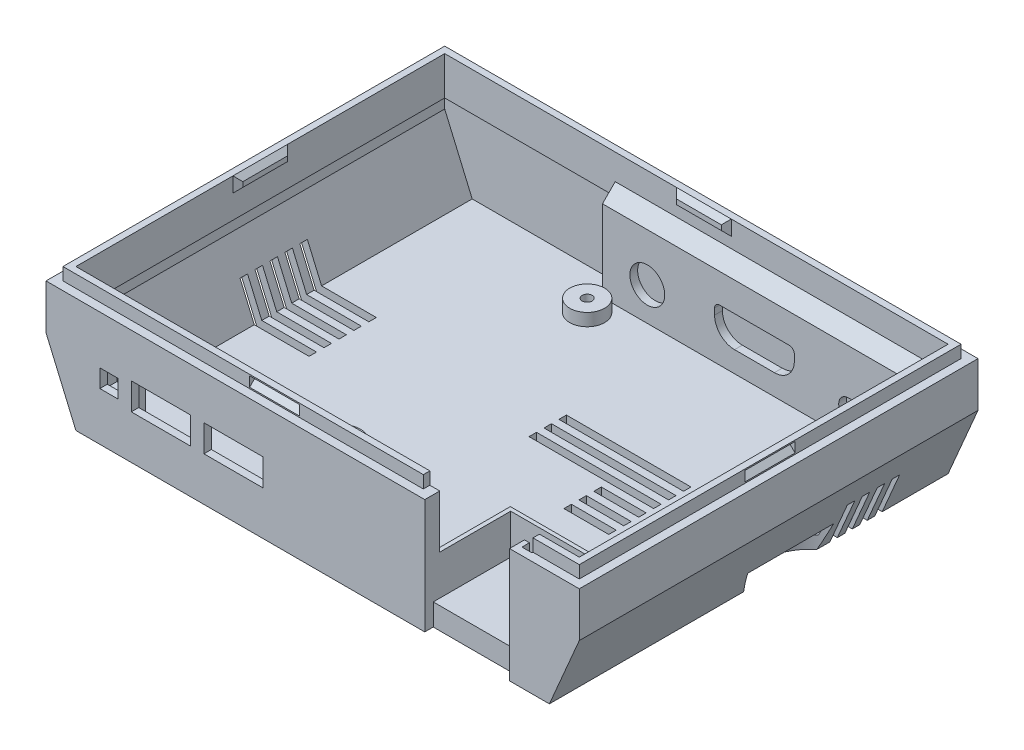
SolidWorks part; units mm, degrees
note: The reader was unsure of these and kept them because the rebuilt part matched: shared geometry of "Sketch7<6>".
ref_plane "Front Plane" through (0, 0, 0) normal (0, 0, 1) x (1, 0, 0)
ref_plane "Top Plane" through (0, 0, 0) normal (0, 1, 0) x (1, 0, 0)
ref_plane "Right Plane" through (0, 0, 0) normal (1, 0, 0) x (0, 0, -1)
sketch "Sketch1" plane through (0, 0, 0) normal (0, 0, 1) x (1, 0, 0)
  line L0 (-41.3082, 11.458) -> (53.6918, 11.458)
  line L1 (-47.3082, 34.458) -> (-47.3082, 25.458)
  line L2 (-47.3082, 25.458) -> (-41.3082, 11.458)
  line L3 (59.6918, 34.458) -> (-47.3082, 34.458)
  line L5 (59.6918, 25.458) -> (53.6918, 11.458)
  line L7 (59.6918, 34.458) -> (59.6918, 25.458)
  dimension "D1" = 95
  dimension "D2" = 107
  dimension "D3" = 9
  dimension "D4" = 107
  dimension "D5" = 23
  dimension "D6" = 6
  dimension "D7" = 9
  dimension "D8" = 11.458
  dimension "D9" = 47.3082
extrude "Boss-Extrude1" add sketch "Sketch1" along normal blind 3
sketch "Sketch2" plane through (0, 0, 3) normal (0, 0, 1) x (1, 0, 0)
  line L0 (-47.3082, 25.458) -> (-41.3082, 11.458) construction
  line L1 (59.6918, 34.458) -> (-47.3082, 34.458) construction
  line L2 (-47.3082, 34.458) -> (-47.3082, 25.458) construction
  line L3 (-47.3082, 34.458) -> (-44.3082, 34.458)
  line L4 (53.6918, 11.458) -> (59.6918, 25.458) construction
  line L5 (59.6918, 34.458) -> (56.6918, 34.458)
  line L6 (-41.3082, 11.458) -> (53.6918, 11.458)
  line L7 (56.6918, 26.0112) -> (56.6918, 34.458)
  line L8 (-44.3082, 26.1347) -> (-38.6611, 12.958)
  line L9 (-44.3082, 34.458) -> (-44.3082, 26.1347)
  line L10 (56.6918, 26.0112) -> (51.7076, 12.958)
  line L14 (59.6918, 25.458) -> (59.6918, 34.458) construction
  line L26 (-47.3082, 34.458) -> (-47.3082, 25.458)
  line L27 (-47.3082, 25.458) -> (-41.3082, 11.458)
  line L28 (53.6918, 11.458) -> (59.6918, 25.458)
  line L29 (59.6918, 25.458) -> (59.6918, 34.458)
  line L34 (-38.6611, 12.958) -> (51.7076, 12.958)
  line L35 (-41.3082, 11.458) -> (53.6918, 11.458) construction
  dimension "D2" = 1.5
extrude "Boss-Extrude2" add sketch "Sketch2" along normal blind 77
sketch "Sketch3" plane through (0, 0, 80) normal (0, 0, 1) x (1, 0, 0)
  line L0 (-47.3082, 34.458) -> (59.6918, 34.458)
  line L12 (-44.3082, 26.1347) -> (-44.3082, 34.458)
  line L13 (-44.3082, 34.458) -> (-47.3082, 34.458)
  line L14 (-47.3082, 34.458) -> (-47.3082, 25.458)
  line L15 (-47.3082, 25.458) -> (-41.3082, 11.458)
  line L16 (-41.3082, 11.458) -> (53.6918, 11.458)
  line L17 (53.6918, 11.458) -> (59.6918, 25.458)
  line L18 (59.6918, 25.458) -> (59.6918, 34.458)
  line L19 (59.6918, 34.458) -> (56.6918, 34.458)
  line L21 (56.6918, 34.458) -> (56.6918, 26.0112)
  line L22 (51.7076, 12.958) -> (-38.6611, 12.958)
  line L25 (56.6918, 26.0112) -> (51.7076, 12.958)
  line L26 (-47.3082, 34.458) -> (-47.3082, 25.458)
  line L27 (-47.3082, 25.458) -> (-41.3082, 11.458)
  line L28 (-41.3082, 11.458) -> (53.6918, 11.458)
  line L29 (53.6918, 11.458) -> (59.6918, 25.458)
  line L30 (59.6918, 25.458) -> (59.6918, 34.458)
  line L32 (-38.6611, 12.958) -> (-44.3082, 26.1347)
  dimension "D1" = 0
extrude "Boss-Extrude3" add sketch "Sketch3" against normal blind 3
sketch "Sketch4" plane through (0, 34.458, 0) normal (0, 1, 0) x (1, 0, 0)
  line L5 (56.6918, -3) -> (-44.3082, -3) construction
  line L7 (56.6918, -77) -> (-44.3082, -77) construction
  line L8 (-45.6082, -78.3) -> (57.9918, -78.3)
  line L9 (57.9918, -78.3) -> (57.9918, -1.7)
  line L10 (57.9918, -1.7) -> (-45.6082, -1.7)
  line L11 (-45.6082, -1.7) -> (-45.6082, -78.3)
  line L12 (-45.6082, -78.3) -> (57.9918, -78.3)
  line L13 (57.9918, -78.3) -> (57.9918, -1.7)
  line L14 (57.9918, -1.7) -> (-45.6082, -1.7)
  line L15 (-45.6082, -1.7) -> (-45.6082, -78.3)
  line L16 (-44.3082, -3) -> (-44.3082, -77)
  line L17 (56.6918, -3) -> (-44.3082, -3)
  line L18 (56.6918, -3) -> (56.6918, -77)
  line L19 (56.6918, -77) -> (-44.3082, -77)
  dimension "D1" = 1.7
extrude "Boss-Extrude4" add sketch "Sketch4" along normal blind 2.5
sketch "Sketch5" plane through (0, 0, 80) normal (0, 0, 1) x (1, 0, 0)
  line L0 (59.6918, 34.458) -> (-47.3082, 34.458) construction
  line L1 (-30.1982, 25.658) -> (-18.3182, 25.658)
  line L2 (-30.1982, 25.658) -> (-30.1982, 20.258)
  line L3 (-30.1982, 20.258) -> (-18.3182, 20.258)
  line L4 (-18.3182, 25.658) -> (-18.3182, 20.258)
  line L5 (-15.6182, 25.658) -> (-3.7382, 25.658)
  line L6 (-15.6182, 25.658) -> (-15.6182, 20.258)
  line L7 (-15.6182, 20.258) -> (-3.7382, 20.258)
  line L8 (-3.7382, 25.658) -> (-3.7382, 20.258)
  line L9 (-36.4982, 24.758) -> (-32.8982, 24.758)
  line L10 (-36.4982, 24.758) -> (-36.4982, 21.158)
  line L11 (-36.4982, 21.158) -> (-32.8982, 21.158)
  line L12 (-32.8982, 24.758) -> (-32.8982, 21.158)
  line L13 (-47.3082, 34.458) -> (-47.3082, 25.458) construction
  line L14 (-45.6082, 34.458) -> (57.9918, 34.458) construction
  dimension "D1" = 5.4
  dimension "D2" = 8.8
  dimension "D3" = 2.7
  dimension "D4" = 5.4
  dimension "D5" = 17.11
  dimension "D6" = 8.8
  dimension "D7" = 9.7
  dimension "D8" = 3.6
  dimension "D9" = 3.6
  dimension "D10" = 10.81
  dimension "D11" = 11.88
  dimension "D12" = 11.88
extrude "Cut-Extrude1" cut sketch "Sketch5" against normal blind 3
sketch "Sketch7" plane through (0, 36.958, 0) normal (0, 1, 0) x (1, 0, 0)
  line L0 (-44.3082, -77) -> (56.6918, -77) construction
  line L1 (29.6918, -77) -> (44.6918, -77)
  line L2 (29.6918, -77) -> (29.6918, -78.3)
  line L3 (29.6918, -78.3) -> (44.6918, -78.3)
  line L4 (44.6918, -77) -> (44.6918, -78.3)
  line L5 (-45.6082, -78.3) -> (57.9918, -78.3) construction
  line L6 (59.6918, -80) -> (59.6918, 0) construction
  line L7 (28.6918, -78.3) -> (45.6918, -78.3)
  line L8 (28.6918, -78.3) -> (28.6918, -81.1052)
  line L9 (28.6918, -81.1052) -> (45.6918, -81.1052)
  line L10 (45.6918, -78.3) -> (45.6918, -81.1052)
  dimension "D1" = 15
  dimension "D2" = 17
  dimension "D3" = 14
  dimension "D4" = 15
extrude "Cut-Extrude4" cut sketch "Sketch7" against normal through all contours L9 L10 L7 L8
extrude "Cut-Extrude5" cut sketch "Sketch7<6>" against normal blind 21.13 contours L1 L4 L3 L2
sketch "Sketch7<6>" plane through (0, 36.958, 0) normal (0, 1, 0) x (1, 0, 0) same geometry as "Sketch7"
sketch "Sketch8" plane through (0, 36.958, 0) normal (0, 1, 0) x (1, 0, 0)
  line L0 (46.1718, -77) -> (48.1718, -77)
  line L1 (44.6918, -77) -> (46.1718, -77)
  line L2 (44.6918, -77) -> (44.6918, -74.2)
  line L3 (44.6918, -74.2) -> (46.1718, -74.2)
  line L5 (44.6918, -77) -> (56.6918, -77) construction
  line L6 (48.1718, -77) -> (46.1718, -74.2)
  dimension "D1" = 1.48
  dimension "D2" = 2.8
  dimension "D3" = 2
extrude "Boss-Extrude5" add sketch "Sketch8" against normal blind 24
sketch "Sketch10" plane through (0, 0, 78.3) normal (0, 0, 1) x (1, 0, 0)
  line L0 (-45.6082, 36.958) -> (29.6918, 36.958) construction
  line L1 (26.7018, 36.958) -> (48.7018, 36.958)
  line L2 (26.7018, 36.958) -> (26.7018, 34.458)
  line L3 (26.7018, 34.458) -> (48.7018, 34.458)
  line L4 (48.7018, 36.958) -> (48.7018, 34.458)
  line L5 (45.6918, 34.458) -> (57.9918, 34.458) construction
  line L6 (57.9918, 36.958) -> (57.9918, 34.458) construction
  point P8 (57.9918, 35.708)
  dimension "D1" = 9.29
  dimension "D2" = 22
extrude "Cut-Extrude6" cut sketch "Sketch10" against normal blind 5
sketch "Sketch11" plane through (0, 12.958, 0) normal (0, 1, 0) x (1, 0, 0)
  line L1 (44.6918, -77) -> (28.9318, -77)
  line L2 (44.6918, -77) -> (44.6918, -62)
  line L3 (44.6918, -62) -> (28.9318, -62)
  line L4 (28.9318, -77) -> (28.9318, -62)
  dimension "D1" = 15
  dimension "D2" = 15.76
extrude "Boss-Extrude6" add sketch "Sketch11" along normal blind 2.87
sketch "Sketch12" plane through (0, 15.828, 0) normal (0, 1, 0) x (1, 0, 0)
  line L5 (29.6918, -76.24) -> (29.6918, -77)
  line L6 (28.9318, -77) -> (29.6918, -77) construction
  line L7 (29.6918, -76.24) -> (30.4518, -76.24)
  line L9 (43.9318, -62.76) -> (44.6918, -62.76)
  line L10 (43.9318, -77.54) -> (43.9318, -74.2)
  line L11 (43.9318, -74.2) -> (43.9318, -62.76)
  line L12 (43.9318, -62.76) -> (29.6918, -62.76)
  line L13 (29.6918, -62.76) -> (29.6918, -76.24)
  line L15 (30.4518, -76.24) -> (30.4518, -77.54)
  line L16 (30.4518, -77.54) -> (43.9318, -77.54)
  line L17 (43.9318, -62.76) -> (29.6918, -62.76)
  line L18 (29.6918, -62.76) -> (29.6918, -76.24)
  line L21 (28.9318, -77) -> (44.6918, -77)
  line L22 (28.9318, -62) -> (28.9318, -77)
  line L23 (44.6918, -62) -> (28.9318, -62)
  line L24 (44.6918, -77) -> (44.6918, -62)
  line L25 (28.9318, -77) -> (29.6918, -77)
  line L26 (28.9318, -62) -> (28.9318, -77)
  line L27 (44.6918, -62) -> (28.9318, -62)
  line L28 (44.6918, -62.76) -> (44.6918, -62)
  dimension "D1" = 0.76
  dimension "D2" = 0
extrude "Boss-Extrude7" add sketch "Sketch12" along normal blind 8
sketch "Sketch15" plane through (-44.3082, 0, 0) normal (1, 0, 0) x (0, 0, -1)
  line L0 (-3, 36.958) -> (-77, 36.958) construction
  line L1 (-45.5, 36.958) -> (-34.5, 36.958)
  line L2 (-45.5, 36.958) -> (-45.5, 33.958)
  line L3 (-45.5, 33.958) -> (-34.5, 33.958)
  line L4 (-34.5, 36.958) -> (-34.5, 33.958)
  line L5 (-77, 26.1347) -> (-77, 36.958) construction
  dimension "D1" = 3
  dimension "D2" = 11
  dimension "D3" = 31.5
extrude "Boss-Extrude8" add sketch "Sketch15" along normal blind 1
chamfer "Chamfer2" distance 1 angle 45 4 edges at (-43.3082, 35.458, 34.5) (-43.3082, 33.958, 40) (-43.3082, 35.458, 45.5) (-43.3082, 36.958, 40)
sketch "Sketch16" plane through (-45.6082, 0, 0) normal (-1, 0, 0) x (0, 0, 1)
  line L0 (1.7, 36.958) -> (78.3, 36.958) construction
  line L1 (35, 36.708) -> (45, 36.708)
  line L2 (35, 36.708) -> (35, 34.708)
  line L3 (35, 34.708) -> (45, 34.708)
  line L4 (45, 36.708) -> (45, 34.708)
  line L5 (1.7, 36.958) -> (1.7, 34.458) construction
  point P6 (1.7, 35.708)
  dimension "D1" = 10
  dimension "D2" = 0.25
  dimension "D3" = 2
  dimension "D4" = 33.3
extrude "Cut-Extrude8" cut sketch "Sketch16" against normal blind 1.5
chamfer "Chamfer3" distance 1.5 angle 45 2 edges at (-44.1082, 36.708, 40) (-44.1082, 34.708, 40)
ref_plane "Plane1" through (6.1918, 0, 0) normal (-1, 0, 0) x (0, 0, 1)
mirror "Mirror1" about plane through (6.1918, 0, 0) normal (-1, 0, 0) of "Chamfer3", "Cut-Extrude8", "Chamfer2", "Boss-Extrude8"
ref_plane "Plane2" through (0, 0, 40) normal (0, 0, 1) x (1, 0, 0)
sketch "Sketch34" plane through (40.6642, -5.0481, 3) normal (0, 0, 1) x (1, 0, 0)
  line L1 (-38.4724, 42.006) -> (-27.4724, 42.006)
  line L2 (-38.4724, 42.006) -> (-38.4724, 39.006)
  line L3 (-38.4724, 39.006) -> (-27.4724, 39.006)
  line L4 (-27.4724, 42.006) -> (-27.4724, 39.006)
  line L6 (16.0276, 42.006) -> (-84.9724, 42.006) construction
  line L7 (16.0276, 42.006) -> (16.0276, 31.0593) construction
  dimension "D1" = 3
  dimension "D2" = 11
  dimension "D3" = 0
  dimension "D4" = 43.5
extrude "Boss-Extrude12" add sketch "Sketch34" along normal blind 1
chamfer "Chamfer6" distance 1 angle 45 4 edges at (13.1918, 35.458, 4) (7.6918, 33.958, 4) (2.1918, 35.458, 4) (7.6918, 36.958, 4)
sketch "Sketch37" plane through (46.081, 0.0503, 1.7) normal (0, 0, -1) x (-1, 0, 0)
  line L0 (-11.9108, 36.9076) -> (91.6892, 36.9076) construction
  line L1 (33.3892, 36.6576) -> (43.3892, 36.6576)
  line L2 (33.3892, 36.6576) -> (33.3892, 34.6576)
  line L3 (33.3892, 34.6576) -> (43.3892, 34.6576)
  line L4 (43.3892, 36.6576) -> (43.3892, 34.6576)
  line L6 (-11.9108, 36.9076) -> (-11.9108, 34.4076) construction
  dimension "D1" = 10
  dimension "D2" = 45.3
  dimension "D3" = 2
  dimension "D4" = 0.25
extrude "Cut-Extrude9" cut sketch "Sketch37" against normal blind 1.5
chamfer "Chamfer7" distance 1.5 angle 45 2 edges at (7.6918, 34.708, 3.2) (7.6918, 36.708, 3.2)
sketch "Sketch40" plane through (-26.6694, -5.8319, 77) normal (0, 0, -1) x (-1, 0, 0)
  line L1 (-29.0712, 42.7898) -> (-18.0712, 42.7898)
  line L2 (-29.0712, 42.7898) -> (-29.0712, 39.7898)
  line L3 (-29.0712, 39.7898) -> (-18.0712, 39.7898)
  line L4 (-18.0712, 42.7898) -> (-18.0712, 39.7898)
  line L6 (17.6388, 42.7898) -> (-53.3712, 42.7898) construction
  line L7 (17.6388, 31.9665) -> (17.6388, 42.7898) construction
  dimension "D1" = 3
  dimension "D2" = 11
  dimension "D3" = 0
  dimension "D4" = 35.71
extrude "Boss-Extrude13" add sketch "Sketch40" along normal blind 1
chamfer "Chamfer8" distance 1 angle 45 4 edges at (-8.5982, 35.458, 76) (-3.0982, 33.958, 76) (2.4018, 35.458, 76) (-3.0982, 36.958, 76)
sketch "Sketch43" plane through (-45.2166, -0.4336, 78.3) normal (0, 0, 1) x (1, 0, 0)
  line L1 (37.0684, 37.1416) -> (47.0684, 37.1416)
  line L2 (37.0684, 37.1416) -> (37.0684, 35.1416)
  line L3 (37.0684, 35.1416) -> (47.0684, 35.1416)
  line L4 (47.0684, 37.1416) -> (47.0684, 35.1416)
  line L6 (-0.3916, 37.3916) -> (71.9184, 37.3916) construction
  line L7 (-0.3916, 37.3916) -> (-0.3916, 34.8916) construction
  dimension "D1" = 10
  dimension "D2" = 0.25
  dimension "D3" = 2
  dimension "D4" = 37.46
extrude "Cut-Extrude10" cut sketch "Sketch43" against normal blind 1.5
chamfer "Chamfer9" distance 1.5 angle 45 2 edges at (-3.1482, 36.708, 76.8) (-3.1482, 34.708, 76.8)
sketch "Sketch44" plane through (-47.3082, 0, 0) normal (-1, 0, 0) x (0, 0, 1)
  line L0 (80, 11.458) -> (0, 11.458) construction
  line L1 (43.72, 19.618) -> (45.22, 19.618)
  line L2 (43.72, 19.618) -> (43.72, 11.458)
  line L3 (43.72, 11.458) -> (45.22, 11.458)
  line L4 (45.22, 19.618) -> (45.22, 11.458)
  line L5 (80, 25.458) -> (80, 11.458) construction
  dimension "D1" = 1.5
  dimension "D2" = 8.16
  dimension "D3" = 34.78
extrude "Cut-Extrude11" cut sketch "Sketch44" against normal blind 18
pattern_linear "LPattern1" count 5 spacing 3 along (0, 0, -1) of "Cut-Extrude11"
sketch "Sketch48" plane through (59.6918, 0, 0) normal (1, 0, 0) x (0, 0, -1)
  line L0 (-80, 11.458) -> (0, 11.458) construction
  line L1 (-80, 25.458) -> (-80, 34.458) construction
  line L8 (-22.22, 19.618) -> (-23.72, 19.618)
  line L9 (-23.72, 19.618) -> (-23.72, 11.458)
  line L10 (-23.72, 11.458) -> (-22.22, 11.458)
  line L11 (-22.22, 11.458) -> (-22.22, 19.618)
  dimension "D2" = 1.5
  dimension "D1" = 56.28
  dimension "D3" = 8.16
extrude "Cut-Extrude13" cut sketch "Sketch48" against normal blind 18
pattern_linear "LPattern2" count 4 spacing 3 along (0, 0, -1) of "Cut-Extrude13"
sketch "Sketch49" plane through (0, 12.958, 0) normal (0, 1, 0) x (1, 0, 0)
  line L0 (51.7076, -3) -> (-38.6611, -3) construction
  line L1 (6.7076, -29.6) -> (31.7076, -29.6)
  line L2 (6.7076, -29.6) -> (6.7076, -31.1)
  line L3 (6.7076, -31.1) -> (31.7076, -31.1)
  line L4 (31.7076, -29.6) -> (31.7076, -31.1)
  line L5 (22.7076, -38.6) -> (31.7076, -38.6)
  line L6 (22.7076, -38.6) -> (22.7076, -40.1)
  line L7 (22.7076, -40.1) -> (31.7076, -40.1)
  line L8 (31.7076, -38.6) -> (31.7076, -40.1)
  line L9 (51.7076, -77) -> (51.7076, -23.72) construction
  dimension "D1" = 1.5
  dimension "D2" = 1.5
  dimension "D3" = 9
  dimension "D4" = 25
  dimension "D5" = 9
  dimension "D6" = 26.6
  dimension "D7" = 20
extrude "Cut-Extrude14" cut sketch "Sketch49" against normal up to next
pattern_linear "LPattern3" count 3 spacing 3 along (0, 0, 1) of "Cut-Extrude14"
sketch "Sketch57" plane through (0, 0, 3) normal (0, 0, 1) x (1, 0, 0)
  line L0 (-44.3082, 27.748) -> (-10.0982, 27.748)
  line L1 (-10.0982, 27.748) -> (-10.0982, 12.958)
  line L3 (56.6918, 36.958) -> (56.6918, 26.0112) construction
  line L4 (56.6918, 26.0112) -> (53.208, 12.958)
  line L5 (56.6918, 27.748) -> (56.6918, 26.0112)
  line L7 (51.9018, 13.4665) -> (51.9018, 27.748)
  line L8 (51.9018, 27.748) -> (56.6918, 27.748)
  line L9 (51.9018, 12.958) -> (53.208, 12.958)
  line L10 (13.1918, 33.958) -> (2.1918, 33.958)
  line L11 (2.1918, 33.958) -> (2.1918, 36.958)
  line L12 (2.1918, 36.958) -> (-44.3082, 36.958)
  line L13 (-44.3082, 36.958) -> (-44.3082, 26.1347)
  line L14 (-44.3082, 26.1347) -> (-38.6611, 12.958)
  line L15 (-38.6611, 12.958) -> (51.7076, 12.958)
  line L16 (51.7076, 12.958) -> (56.6918, 26.0112)
  line L17 (56.6918, 26.0112) -> (56.6918, 36.958)
  line L18 (56.6918, 36.958) -> (13.1918, 36.958)
  line L19 (13.1918, 36.958) -> (13.1918, 33.958)
  line L20 (51.9018, 13.4665) -> (51.9018, 12.958)
  line L23 (-44.3082, 27.748) -> (-44.3082, 26.1347)
  line L24 (-44.3082, 26.1347) -> (-38.6611, 12.958)
  line L25 (-38.6611, 12.958) -> (-10.0982, 12.958)
  dimension "D2" = 34.21
  dimension "D3" = 14.79
  dimension "D5" = 62
  dimension "D1" = 0
extrude "Cut-Extrude16" cut sketch "Sketch57" against normal blind 1.5
chamfer "Chamfer11" distance 1.5 angle 45 2 edges at (-27.2032, 27.748, 3) (54.2968, 27.748, 3)
sketch "Sketch59" plane through (0, 0, 1.5) normal (0, 0, 1) x (1, 0, 0)
  line L0 (56.6918, 27.748) -> (58.1918, 27.748)
  line L1 (53.665, 13.4087) -> (58.1918, 25.7447)
  line L2 (58.1918, 25.7447) -> (58.1918, 27.748)
  line L3 (53.208, 12.958) -> (53.4996, 12.958)
  line L4 (56.6918, 26.0112) -> (56.6918, 27.748)
  line L5 (56.6918, 27.748) -> (51.9018, 27.748)
  line L6 (51.9018, 27.748) -> (51.9018, 12.958)
  line L7 (51.9018, 12.958) -> (53.208, 12.958)
  line L8 (56.6918, 26.0112) -> (56.6918, 27.748)
  line L10 (56.6918, 26.0112) -> (51.9018, 13.4665) construction
  line L12 (53.31, 12.4412) -> (58.1918, 25.7447) construction
  line L13 (56.6918, 26.0112) -> (51.9018, 13.4665)
  line L14 (53.665, 13.4087) -> (53.4996, 12.958)
  line L16 (51.9018, 12.958) -> (53.208, 12.958)
  line L17 (-44.3082, 26.1347) -> (-38.6611, 12.958) construction
  line L18 (-44.3082, 26.1347) -> (-38.6611, 12.958)
  line L19 (51.9018, 12.958) -> (56.6918, 26.0112) construction
  line L20 (53.208, 12.958) -> (56.6918, 26.0112)
  line L21 (-44.3082, 27.748) -> (-44.3082, 26.1347) construction
  line L22 (-44.3082, 27.748) -> (-44.3082, 26.1347)
  line L23 (-45.6869, 25.5438) -> (-40.293, 12.958)
  line L24 (-45.8082, 27.748) -> (-45.8082, 26.1347)
  line L25 (-38.6611, 12.958) -> (-40.293, 12.958)
  line L26 (-44.3082, 27.748) -> (-45.8082, 27.748)
  line L27 (-45.6869, 25.5438) -> (-45.8082, 25.8268)
  line L28 (-45.8082, 26.1347) -> (-45.8082, 25.8268)
  line L29 (-45.6869, 25.5438) -> (-40.0398, 12.3671) construction
  line L30 (51.9018, 27.748) -> (51.9018, 12.958) construction
  line L31 (51.9018, 13.4665) -> (51.9018, 12.958)
  dimension "D1" = 0
  dimension "D2" = 1.5
  dimension "D3" = 1.5
  dimension "D4" = 1.5
extrude "Cut-Extrude17" cut sketch "Sketch59" along normal blind 77
chamfer "Chamfer12" distance 1.5 angle 45 2 edges at (56.6918, 27.748, 39.25) (-44.3082, 27.748, 39.25)
sketch "Sketch62" plane through (0, 0, 3) normal (0, 0, 1) x (1, 0, 0)
  line L0 (51.9018, 29.248) -> (51.9018, 13.4665) construction
  line L1 (51.9018, 29.248) -> (51.9018, 13.4665)
  line L3 (51.7076, 12.958) -> (-10.0982, 12.958) construction
  line L4 (-10.0982, 12.958) -> (-10.0982, 29.248) construction
  line L5 (51.9018, 13.4665) -> (51.7076, 12.958)
  line L6 (51.7076, 12.958) -> (-10.0982, 12.958)
  line L7 (-10.0982, 12.958) -> (-10.0982, 29.248)
  line L8 (-10.0982, 29.248) -> (51.9018, 29.248)
extrude "Boss-Extrude16" add sketch "Sketch62" along normal blind 2.56
chamfer "Chamfer13" distance 2.56 angle 45 1 edges at (20.9018, 29.248, 3)
sketch "Sketch64" plane through (0, 0, 5.56) normal (0, 0, 1) x (1, 0, 0)
  line L0 (51.7076, 12.958) -> (51.9018, 13.4665) construction
  line L2 (51.7076, 12.958) -> (51.9018, 13.4665)
  line L4 (51.9018, 13.4665) -> (51.9018, 12.958)
  line L6 (51.9018, 12.958) -> (51.7076, 12.958)
extrude "Cut-Extrude18" cut sketch "Sketch64" along normal blind 72.94
sketch "Sketch66" plane through (0, 0, 77) normal (0, 0, -1) x (-1, 0, 0)
  line L0 (-56.6918, 26.0112) -> (-51.7076, 12.958) construction
  line L1 (44.3082, 26.1347) -> (44.3082, 27.748) construction
  line L2 (38.6611, 12.958) -> (44.3082, 26.1347) construction
  line L3 (-56.6918, 26.0112) -> (-56.6918, 27.748) construction
  line L4 (44.3082, 26.1347) -> (44.3082, 27.748)
  line L5 (38.6611, 12.958) -> (44.3082, 26.1347)
  line L6 (44.3082, 27.748) -> (-26.9118, 27.748)
  line L7 (-26.9118, 27.748) -> (-26.9118, 12.958)
  line L8 (-26.9118, 12.958) -> (38.6611, 12.958)
  line L11 (-48.1718, 12.958) -> (-48.1718, 34.458) construction
  line L12 (-51.7076, 12.958) -> (-48.1718, 12.958) construction
  line L13 (-56.6918, 26.0112) -> (-51.7076, 12.958)
  line L14 (-56.6918, 26.0112) -> (-56.6918, 27.748)
  line L17 (-48.1718, 12.958) -> (-48.1718, 27.748)
  line L18 (-51.7076, 12.958) -> (-48.1718, 12.958)
  line L20 (-56.6918, 27.748) -> (-48.1718, 27.748)
extrude "Cut-Extrude19" cut sketch "Sketch66" against normal blind 1.5
chamfer "Chamfer14" distance 1.5 angle 45 1 edges at (53.1818, 27.748, 77)
sketch "Sketch67" plane through (0, 0, 78.5) normal (0, 0, -1) x (-1, 0, 0)
  line L0 (40.293, 12.958) -> (-26.9118, 12.958) construction
  line L1 (38.5982, 12.958) -> (31.2982, 12.958)
  line L2 (32.8982, 21.158) -> (32.8982, 24.758) construction
  line L3 (36.4982, 24.758) -> (36.4982, 21.158) construction
  line L4 (32.8982, 24.758) -> (36.4982, 24.758) construction
  line L5 (36.4982, 21.158) -> (32.8982, 21.158) construction
  line L6 (32.8982, 21.158) -> (32.8982, 24.758)
  line L7 (36.4982, 24.758) -> (36.4982, 21.158)
  line L8 (32.8982, 24.758) -> (36.4982, 24.758)
  line L9 (36.4982, 21.158) -> (32.8982, 21.158)
  line L10 (38.5982, 12.958) -> (38.5982, 25.758)
  line L11 (38.5982, 25.758) -> (37.0982, 25.758)
  line L12 (37.0982, 25.758) -> (37.0982, 20.058)
  line L13 (37.0982, 20.058) -> (35.5982, 20.058)
  line L14 (35.5982, 20.058) -> (35.5982, 12.958)
  line L15 (33.7982, 12.958) -> (33.7982, 20.058)
  line L16 (33.7982, 20.058) -> (32.2982, 20.058)
  line L17 (32.2982, 20.058) -> (32.2982, 25.758)
  line L18 (32.2982, 25.758) -> (31.2982, 25.758)
  line L19 (31.2982, 25.758) -> (31.2982, 12.958)
  line M4 (-26.9118, 12.958) -> (40.293, 12.958)
  dimension "D1" = 0.6
  dimension "D2" = 0.6
  dimension "D3" = 1
  dimension "D4" = 1.5
  dimension "D5" = 12.8
  dimension "D6" = 12.8
  dimension "D7" = 7.1
  dimension "D8" = 1.8
  dimension "D9" = 2.5
extrude "Boss-Extrude17" add sketch "Sketch67" along normal blind 2.5 contours L18 L19 L15 L16 L17 M4 | L13 L14 L1 L10 L11 L12
sketch "Sketch50" plane through (0, 12.958, 0) normal (0, 1, 0) x (1, 0, 0)
  line L1 (-10.0982, -5.56) -> (51.9018, -5.56) construction
  line L2 (53.4996, -13.22) -> (53.4996, -1.5) construction
  circle A0 centre (48.9846, -9.71) radius 3.5
  circle A1 centre (48.9846, -9.71) radius 1
  dimension "D5" = 7
  dimension "D6" = 2
  dimension "D1" = 4.515
  dimension "D4" = 4.15
extrude "Boss-Extrude18" add sketch "Sketch50" along normal blind 2.5
pattern_linear "LPattern4" count 2 spacing 58 along (-1, 0, 0) count 2 spacing 49 along (0, 0, 1) of "Boss-Extrude18"
sketch "Sketch68" plane through (0, 0, 5.56) normal (0, 0, 1) x (1, 0, 0)
  line L0 (51.9018, 18.198) -> (46.3018, 18.198)
  line L1 (51.9018, 12.958) -> (51.9018, 29.248) construction
  line L2 (41.8018, 20.198) -> (41.8018, 16.198) construction
  line L3 (-10.0982, 12.958) -> (51.9018, 12.958) construction
  line L4 (39.3018, 20.198) -> (44.3018, 20.198)
  line L5 (39.3018, 16.198) -> (44.3018, 16.198)
  line L7 (41.9875, 18.198) -> (40.9875, 18.198)
  line L8 (12.4018, 23.398) -> (28.4018, 23.398)
  line L9 (12.4018, 23.398) -> (12.4018, 17.148)
  line L11 (12.4018, 17.148) -> (28.4018, 17.148)
  line L12 (28.4018, 23.398) -> (28.4018, 17.148)
  arc A0 (44.3018, 16.198) -> (44.3018, 20.198) centre (44.3018, 18.198) ccw
  arc A1 (39.3018, 20.198) -> (39.3018, 16.198) centre (39.3018, 18.198) ccw
  circle A2 centre (-1.0982, 19.638) radius 3.5
  dimension "D3" = 4
  dimension "D4" = 4
  dimension "D6" = 7
  dimension "D1" = 5.24
  dimension "D2" = 5
  dimension "D5" = 7.6
  dimension "D7" = 6.68
  dimension "D8" = 13.5
  dimension "D9" = 6.25
  dimension "D10" = 16
  dimension "D11" = 4.19
  dimension "D12" = 13.4
sketch "Sketch69" plane through (0, 0, 0) normal (0, 0, -1) x (-1, 0, 0)
  line L0 (41.3082, 11.458) -> (-53.6918, 11.458) construction
  line L1 (-50.9018, 11.458) -> (9.0982, 11.458)
  line L2 (-50.9018, 11.458) -> (-50.9018, 29.958)
  line L3 (-50.9018, 29.958) -> (9.0982, 29.958)
  line L4 (9.0982, 11.458) -> (9.0982, 29.958)
  line L5 (-59.6918, 25.458) -> (-59.6918, 34.458) construction
  dimension "D1" = 18.5
  dimension "D2" = 60
  dimension "D3" = 8.79
extrude "Cut-Extrude20" cut sketch "Sketch69" against normal blind 4
chamfer "Chamfer15" distance 1.5 angle 45 1 edges at (20.9018, 29.958, 4)
extrude "Cut-Extrude21" cut sketch "Sketch68" against normal up to next
fillet "Fillet1" radius 4 2 edges at (12.4018, 17.148, 4.78) (28.4018, 17.148, 4.78)
fillet "Fillet2" radius 1 2 edges at (12.4018, 23.398, 4.78) (28.4018, 23.398, 4.78)
ref_plane "Plane3" through (0, 0, 43.18) normal (0, 0, -1) x (-1, 0, 0)
sketch "Sketch71" plane through (0, 0, 43.18) normal (0, 0, -1) x (-1, 0, 0)
  line L1 (-53.4996, 12.958) -> (-58.1918, 25.7447) construction
  line L2 (-45.4996, 12.958) -> (-53.4996, 12.958)
  line L3 (-53.4996, 12.958) -> (-53.8666, 13.958)
  line L4 (-45.4996, 12.958) -> (-45.4996, 13.958)
  line L5 (-45.4996, 13.958) -> (-53.8666, 13.958)
  dimension "D1" = 1
  dimension "D2" = 8
extrude "Boss-Extrude19" add sketch "Sketch71" along normal blind 19
sketch "Sketch72" plane through (0, 11.458, 0) normal (0, -1, 0) x (1, 0, 0)
  line L4 (53.6918, 80) -> (53.6918, 23.72) construction
  line L6 (45.6918, 80) -> (53.6918, 80) construction
  arc A0 (53.6918, 41.03) -> (53.6918, 26.34) centre (59.5818, 33.685) ccw
  circle A1 centre (59.5818, 33.685) radius 9.4149
  dimension "D3" = 53.66
  dimension "D2" = 5.89
  dimension "D1" = 38.97
extrude "Cut-Extrude23" cut sketch "Sketch72" against normal blind 4.9 contours A0 A1
sketch "Sketch73" plane through (0, 23.828, 0) normal (0, 1, 0) x (1, 0, 0)
  line L0 (28.6918, -78.3) -> (29.6918, -78.3) construction
  line L1 (26.7018, -77) -> (29.6918, -77) construction
  line L2 (29.6918, -77) -> (29.6918, -78.3) construction
  line L3 (29.6918, -62.76) -> (28.9318, -62.76)
  line L4 (29.6918, -77) -> (29.6918, -62.76) construction
  line L5 (28.9318, -62) -> (28.9318, -77) construction
  line L7 (44.6918, -74.2) -> (44.6918, -78.3) construction
  line L8 (44.6918, -78.3) -> (45.6918, -78.3) construction
  line L9 (46.1718, -74.2) -> (44.6918, -74.2) construction
  line L10 (29.6918, -62.76) -> (44.6918, -62.76)
  line L13 (28.6918, -78.3) -> (29.6918, -78.3)
  line L14 (28.6918, -77) -> (28.9318, -77)
  line L15 (29.6918, -77) -> (29.6918, -78.3)
  line L16 (44.6918, -62.76) -> (44.6918, -74.2)
  line L17 (29.6918, -77) -> (29.6918, -62.76)
  line L18 (28.6918, -78.3) -> (28.6918, -77)
  line L19 (28.6918, -77) -> (28.9318, -77)
  line L20 (44.6918, -74.2) -> (44.6918, -78.3)
  line L21 (44.6918, -78.3) -> (45.6918, -78.3)
  line L22 (45.6918, -74.2) -> (44.6918, -74.2)
  line L23 (28.6918, -77) -> (28.6918, -62.76)
  line L24 (28.6918, -62.76) -> (28.9318, -62.76)
  line L26 (45.6918, -78.3) -> (45.6918, -74.2)
  line L29 (45.6918, -74.2) -> (45.6918, -78.3)
  line L33 (44.6918, -74.2) -> (44.6918, -78.3) construction
  line L36 (29.6918, -77) -> (29.6918, -78.3)
  line L37 (44.6918, -74.2) -> (44.6918, -78.3)
extrude "EvanUSB1" cut sketch "Sketch73" against normal blind 8 and the other way through all
sketch "Sketch75" plane through (0, 15.828, 0) normal (0, 1, 0) x (1, 0, 0)
  line L0 (28.9318, -62.76) -> (28.9318, -77) construction
  line L1 (28.9318, -62.76) -> (28.9318, -77)
  line L2 (28.9318, -62) -> (28.9318, -62.76)
  line L3 (28.6918, -77) -> (28.9318, -77) construction
  line L4 (28.9318, -62) -> (27.8618, -62)
  line L5 (44.6918, -74.2) -> (45.6918, -74.2)
  line L6 (45.6918, -74.2) -> (45.6918, -62.76)
  line L7 (44.6918, -62.76) -> (44.6918, -62)
  line L8 (44.6918, -62.76) -> (45.6918, -62.76)
  line L9 (27.8618, -62) -> (27.8618, -77)
  line L10 (44.6918, -62) -> (28.9318, -62) construction
  line L11 (44.6918, -74.2) -> (44.6918, -62.76)
  line L12 (44.6918, -62) -> (28.9318, -62) construction
  line L13 (44.6918, -62) -> (45.6918, -62)
  line L14 (45.6918, -62) -> (45.6918, -62.76)
  line L15 (28.6918, -77) -> (28.9318, -77)
  line L16 (28.6918, -77) -> (28.6918, -62)
  line L17 (28.6918, -77) -> (27.8618, -77)
  line L18 (28.9318, -62) -> (28.9318, -77) construction
  line L28 (45.6918, -74.2) -> (44.6918, -74.2) construction
  line L38 (45.6918, -74.2) -> (44.6918, -74.2)
  line M27 (28.9318, -62.76) -> (28.9318, -77)
  line M28 (28.9318, -77) -> (28.6918, -77)
  dimension "D1" = 0.83
extrude "Boss-Extrude27" add sketch "Sketch75" against normal blind 2.87 contours L11 L5 L6 L8 | L14 L13 L7 L8 | L17 L16 L4 L9 | L16 L2 L4 M28 M27
sketch "Sketch76" plane through (0, 15.828, 0) normal (0, 1, 0) x (1, 0, 0)
  line L0 (27.8618, -62) -> (27.8618, -77) construction
  line L1 (28.9318, -62) -> (27.8618, -62) construction
  line L2 (28.6918, -77) -> (27.8618, -77) construction
  line L3 (44.6918, -62) -> (45.6918, -62) construction
  line L4 (44.6918, -62.76) -> (44.6918, -62) construction
  line L5 (45.6918, -74.2) -> (45.6918, -62) construction
  line L6 (27.8618, -62) -> (27.8618, -77)
  line L7 (28.9318, -62) -> (27.8618, -62)
  line L8 (28.6918, -77) -> (27.8618, -77)
  line L9 (44.6918, -62) -> (45.6918, -62)
  line L10 (44.6918, -62.76) -> (44.6918, -62)
  line L11 (45.6918, -62.76) -> (45.6918, -62)
  line L12 (28.6918, -77) -> (28.6918, -62.76)
  line L13 (44.6918, -62.76) -> (45.6918, -62.76)
  line L14 (28.6918, -62.76) -> (28.9318, -62.76)
  line L15 (28.9318, -62.76) -> (28.9318, -62)
extrude "EvanUSB3" add sketch "Sketch76" along normal blind 8
sketch "Sketch81" plane through (0, 34.458, 0) normal (0, 1, 0) x (1, 0, 0)
  line L0 (48.1718, -77) -> (45.6918, -77)
  line L1 (45.6918, -80) -> (45.6918, -74.2) construction
  line L2 (46.1718, -74.2) -> (45.6918, -74.2) construction
  line L3 (48.1718, -77) -> (46.1718, -74.2) construction
  line L4 (45.6918, -77) -> (45.6918, -74.2)
  line L5 (46.1718, -74.2) -> (45.6918, -74.2)
  line L6 (48.1718, -77) -> (46.1718, -74.2)
extrude "Cut-Extrude24" cut sketch "Sketch81" against normal blind 21.5
sketch "Sketch82" plane through (0, 0, 77) normal (0, 0, -1) x (-1, 0, 0)
  line L2 (-48.1718, 27.748) -> (-46.6918, 27.748)
  line L4 (-46.6918, 12.958) -> (-46.6918, 27.748)
  line L9 (-56.6918, 36.958) -> (-56.6918, 29.248)
  line L10 (-56.6918, 29.248) -> (-48.1718, 29.248)
  line L11 (-48.1718, 29.248) -> (-48.1718, 12.958)
  line L12 (-48.1718, 12.958) -> (-45.6918, 12.958)
  line L13 (-45.6918, 12.958) -> (-45.6918, 15.828)
  line L14 (-45.6918, 15.828) -> (-45.6918, 34.458)
  line L15 (-45.6918, 34.458) -> (-48.7018, 34.458)
  line L16 (-48.7018, 34.458) -> (-48.7018, 36.958)
  line L17 (-48.7018, 36.958) -> (-56.6918, 36.958)
  line L20 (-48.1718, 27.748) -> (-48.1718, 12.958)
  line L21 (-48.1718, 12.958) -> (-46.6918, 12.958)
  dimension "D1" = 0
extrude "Cut-Extrude25" cut sketch "Sketch82" against normal up to vertex
sketch "Sketch77" plane through (0, 0, 0) normal (0, 0, -1) x (-1, 0, 0)
  line L0 (-50.9018, 11.458) -> (9.0982, 11.458) construction
  line L1 (-49.9018, 11.458) -> (8.0982, 11.458)
  line L2 (-50.9018, 29.958) -> (-50.9018, 11.458) construction
  line L3 (-49.9018, 11.458) -> (8.0982, 11.458)
  line L4 (-49.9018, 11.458) -> (-49.9018, 29.458)
  line L5 (-49.9018, 29.458) -> (8.0982, 29.458)
  line L6 (8.0982, 11.458) -> (8.0982, 29.458)
  line L7 (9.0982, 11.458) -> (9.0982, 29.958) construction
  dimension "D1" = 18
  dimension "D2" = 1
  dimension "D3" = 1
extrude "Support_Back" add sketch "Sketch77" against normal blind 2.5 separate body contours L1 L6 L5 L4
ref_plane "Plane5" [suppressed] through (0, 15.858, 0) normal (0, -1, 0) x (-1, 0, 0)
sketch "Sketch79" [suppressed] plane through (0, 15.858, 0) normal (0, -1, 0) x (-1, 0, 0)
  line L1 (-55.9171, -26.2309) -> (-55.9171, -41.1837)
  line L3 (-54.4015, -27.3467) -> (-54.8769, -26.9395)
  line L4 (-55.4171, -40.826) -> (-55.9171, -41.1837)
  line L5 (-55.4171, -25.6583) -> (-55.4171, -40.826) construction
  line L6 (-55.9171, -25.6583) -> (-55.9171, -41.7117) construction
  line L7 (-54.0695, -26.9727) -> (-54.5516, -26.5598) construction
  arc A0 (-55.4171, -40.826) -> (-55.2136, -40.6844) centre (-60.2361, -33.685) ccw
  arc A1 (-55.2136, -40.6844) -> (-54.4078, -40.0291) centre (-60.2361, -33.685) ccw
  arc A2 (-54.4078, -40.0291) -> (-54.4015, -27.3467) centre (-60.2361, -33.685) ccw
  arc A3 (-55.2136, -26.6856) -> (-55.9171, -26.2309) centre (-60.2361, -33.685) ccw
  arc A4 (-54.8466, -26.9641) -> (-55.9171, -26.2309) centre (-60.2361, -33.685) ccw
  arc A15 (-55.9171, -41.7117) -> (-54.9222, -41.0907) centre (-60.2361, -33.685) ccw construction
  arc A16 (-54.9222, -41.0907) -> (-54.0695, -40.3973) centre (-60.2361, -33.685) ccw construction
  arc A17 (-54.0695, -40.3973) -> (-54.0695, -26.9727) centre (-60.2361, -33.685) ccw construction
  dimension "D1" = 0.5
extrude "Boss-Extrude30" [suppressed] add sketch "Sketch79" along normal blind 4.4 separate body
sketch "Sketch80" [suppressed] plane through (55.9171, 0, 0) normal (1, 0, 0) x (0, 0, -1)
  line L4 (-26.2309, 15.858) -> (-41.1837, 15.858)
  line L5 (-26.2309, 11.458) -> (-26.2309, 15.858)
  line L6 (-41.1837, 11.458) -> (-26.2309, 11.458)
  line L7 (-41.1837, 15.858) -> (-41.1837, 11.458)
  line L8 (-26.2309, 15.858) -> (-41.1837, 15.858)
  line L9 (-26.2309, 11.458) -> (-26.2309, 15.858)
  line L10 (-41.1837, 11.458) -> (-26.2309, 11.458)
  line L11 (-41.1837, 15.858) -> (-41.1837, 11.458)
  dimension "D1" = 0
extrude "Boss-Extrude31" [suppressed] add sketch "Sketch80" along normal blind 2
chamfer "Chamfer16" distance 1.5 angle 45 1 edges at (47.4318, 27.748, 77)
sketch "Sketch83" plane through (0, 34.458, 0) normal (0, 1, 0) x (1, 0, 0)
  line L1 (46.6918, -78.5) -> (53.4996, -78.5) construction
  line L2 (46.6918, -78.5) -> (46.6918, -77) construction
  line L4 (48.7018, -78.5) -> (48.7018, -77)
  line L5 (46.6918, -78.5) -> (48.7018, -78.5)
  line L6 (46.6918, -78.5) -> (46.6918, -77)
  line L7 (48.7018, -77) -> (46.6918, -77)
  line L8 (46.6918, -77) -> (46.6998, -76.9981)
  line M1 (48.7018, -77) -> (45.6918, -77)
  line M16 (48.7018, -78.3) -> (48.7018, -77)
extrude "Cut-Extrude26" cut sketch "Sketch83" against normal blind 21.5 contours L6 L5 L4 M16 M1
